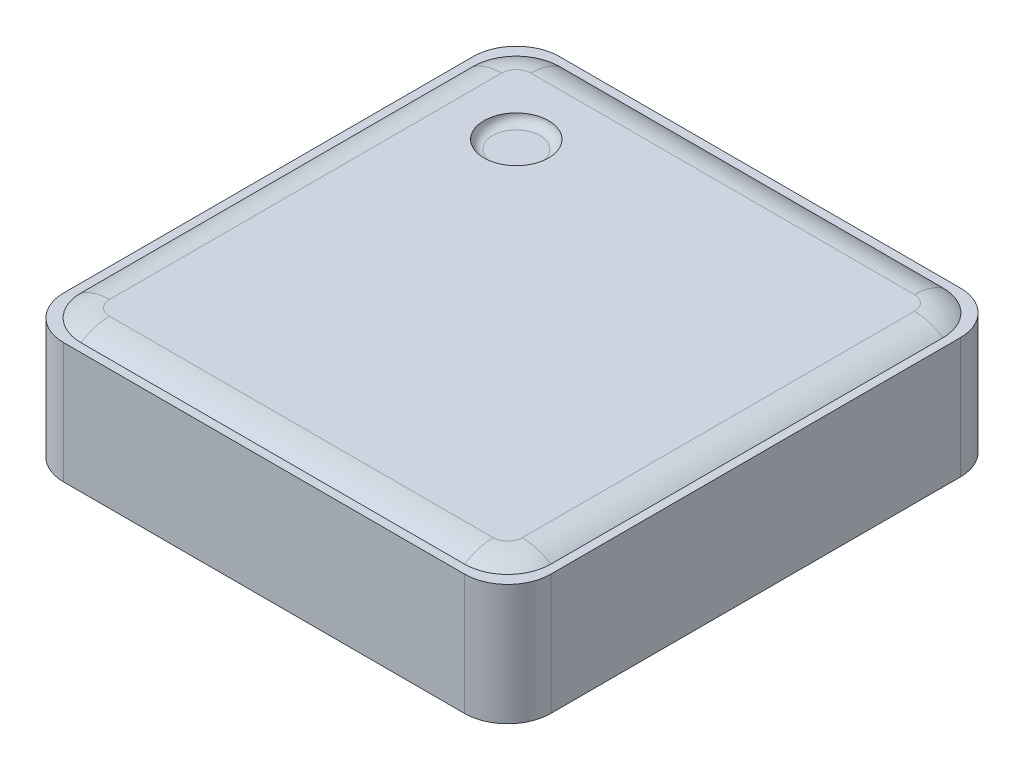
SolidWorks part; units mm, degrees
material "PVC Rígido"
ref_plane "Plano frontal" through (0, 0, 0) normal (0, 0, 1) x (1, 0, 0)
ref_plane "Plano superior" through (0, 0, 0) normal (0, 1, 0) x (1, 0, 0)
ref_plane "Plano direito" through (0, 0, 0) normal (1, 0, 0) x (0, 0, -1)
sketch "Esboço1" plane through (0, 0, 0) normal (0, 1, 0) x (1, 0, 0)
  line L1 (56.5, 57.5) -> (-56.5, 57.5)
  line L2 (56.5, 57.5) -> (56.5, -57.5)
  line L3 (56.5, -57.5) -> (-56.5, -57.5)
  line L4 (-56.5, 57.5) -> (-56.5, -57.5)
  line L5 (56.5, 57.5) -> (-56.5, -57.5) construction
  line L6 (56.5, -57.5) -> (-56.5, 57.5) construction
  point P0 (0, 0)
  dimension "D1" = 115
  dimension "D2" = 113
extrude "Ressalto-extrusão1" add sketch "Esboço1" along normal blind 30
sketch "Esboço2" plane through (0, 30, 0) normal (0, 1, 0) x (1, 0, 0)
  line L1 (-54.5, 55.5) -> (54.5, 55.5)
  line L2 (-54.5, 55.5) -> (-54.5, -55.5)
  line L3 (-54.5, -55.5) -> (54.5, -55.5)
  line L4 (54.5, 55.5) -> (54.5, -55.5)
  line L5 (-54.5, 55.5) -> (54.5, -55.5) construction
  line L6 (-54.5, -55.5) -> (54.5, 55.5) construction
  line L7 (-56.5, 57.5) -> (56.5, 57.5)
  line L8 (-56.5, 57.5) -> (-56.5, -57.5)
  line L9 (-56.5, -57.5) -> (56.5, -57.5)
  line L10 (56.5, 57.5) -> (56.5, -57.5)
  line L11 (-56.5, 57.5) -> (56.5, -57.5) construction
  line L12 (-56.5, -57.5) -> (56.5, 57.5) construction
  point P0 (0, 0)
  point P6 (0, 0)
  dimension "D1" = 2
  dimension "D2" = 2
extrude "Corte-extrusão1" cut sketch "Esboço2" against normal blind 2
fillet "Filete1" radius 10 8 edges at (54.5, 29, -55.5) (54.5, 29, 55.5) (-54.5, 29, 55.5) (-54.5, 29, -55.5) (56.5, 14, 57.5) (56.5, 14, -57.5) (-56.5, 14, 57.5) (-56.5, 14, -57.5)
fillet "Filete2" radius 12 8 edges at (51.5711, 30, 52.5711) (0, 30, 55.5) (-51.5711, 30, 52.5711) (-54.5, 30, 0) (-51.5711, 30, -52.5711) (0, 30, -55.5) (51.5711, 30, -52.5711) (54.5, 30, 0)
sketch "Esboço3" plane through (0, 30, 0) normal (0, 1, 0) x (1, 0, 0)
  line L1 (-47.8668, 45.5) -> (-47.8668, -45.5) construction
  line L2 (44.5, 48.8668) -> (-44.5, 48.8668) construction
  circle A0 centre (-32.8668, 33.8668) radius 7.5
  point P2 (0, 0)
  dimension "D1" = 15
  dimension "D3" = 15
  dimension "D2" = 15
extrude "Corte-extrusão2" cut sketch "Esboço3" against normal blind 2
fillet "Filete3" radius 2 1 edges at (-32.8668, 28, -26.3668) type face fillet first side face at (-32.8668, 28, -26.3668) second side face at (-32.8668, 28, -26.3668)
